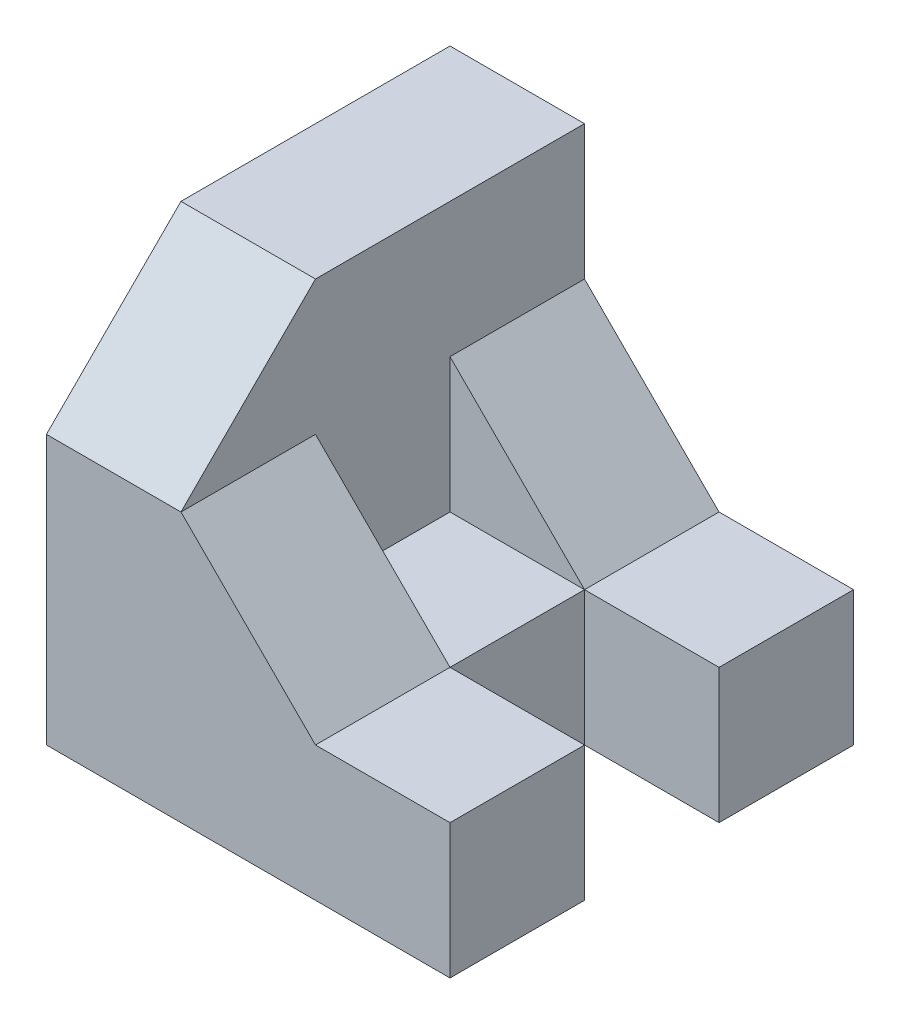
SolidWorks part; units mm, degrees
ref_plane "Alzado" through (0, 0, 0) normal (0, 0, 1) x (1, 0, 0)
ref_plane "Planta" through (0, 0, 0) normal (0, 1, 0) x (1, 0, 0)
ref_plane "Vista lateral" through (0, 0, 0) normal (1, 0, 0) x (0, 0, -1)
sketch "Croquis1" plane through (0, 0, 0) normal (0, 1, 0) x (1, 0, 0)
  line L0 (30, 10) -> (10, 10)
  line L1 (30, 30) -> (-30, 30)
  line L2 (30, 30) -> (30, 10)
  line L3 (30, -30) -> (-30, -30)
  line L4 (-30, 30) -> (-30, -30)
  line L5 (30, 30) -> (-30, -30) construction
  line L6 (30, -30) -> (-30, 30) construction
  line L7 (10, 10) -> (10, -10)
  line L8 (10, -10) -> (30, -10)
  line L9 (30, -10) -> (30, -30)
  point P0 (0, 0)
  point P8 (10, 0)
  dimension "D1" = 60
  dimension "D2" = 60
  dimension "D3" = 20
  dimension "D4" = 20
extrude "Saliente-Extruir1" add sketch "Croquis1" along normal blind 20
sketch "Croquis2" plane through (0, 20, 0) normal (0, 1, 0) x (1, 0, 0)
  line L0 (10, -10) -> (10, -30)
  line L1 (10, 10) -> (10, 30)
  line L2 (10, 10) -> (-10, 10)
  line L3 (-10, 10) -> (-10, -10)
  line L4 (-10, -10) -> (10, -10)
  line L8 (-30, 30) -> (-30, -30)
  line L9 (-30, -30) -> (30, -30)
  line L10 (30, -30) -> (30, -10)
  line L11 (30, -10) -> (10, -10)
  line L12 (10, -10) -> (10, 10)
  line L13 (10, 10) -> (30, 10)
  line L14 (30, 10) -> (30, 30)
  line L15 (30, 30) -> (-30, 30)
  line L16 (-30, 30) -> (-30, -30)
  line L17 (-30, -30) -> (10, -30)
  line L23 (10, 30) -> (-30, 30)
  dimension "D2" = 20
  dimension "D1" = 0
extrude "Saliente-Extruir2" add sketch "Croquis2" along normal blind 20 contours L16 L17 L0 L4 L3 L2 L1 L23
chamfer "Chaflán1" distance 20 1 edges at (10, 40, 20)
chamfer "Chaflán2" distance 20 angle 45 1 edges at (10, 40, -20)
sketch "Croquis3" plane through (0, 40, 0) normal (0, 1, 0) x (1, 0, 0)
  line L6 (-10, -10) -> (-10, 10)
  line L7 (-10, 10) -> (-10, 30)
  line L8 (-10, 30) -> (-30, 30)
  line L9 (-30, 30) -> (-30, -30)
  line L10 (-30, -30) -> (-10, -30)
  line L11 (-10, -30) -> (-10, -10)
  line L12 (-10, -10) -> (-10, 10)
  line L13 (-10, 10) -> (-10, 30)
  line L14 (-10, 30) -> (-30, 30)
  line L15 (-30, 30) -> (-30, -30)
  line L16 (-30, -30) -> (-10, -30)
  line L17 (-10, -30) -> (-10, -10)
  dimension "D1" = 0
extrude "Saliente-Extruir3" add sketch "Croquis3" along normal blind 20 contours L12 L13 L14 L15 L16 L17
chamfer "Chaflán3" distance 20 angle 45 1 edges at (-20, 60, 30)
